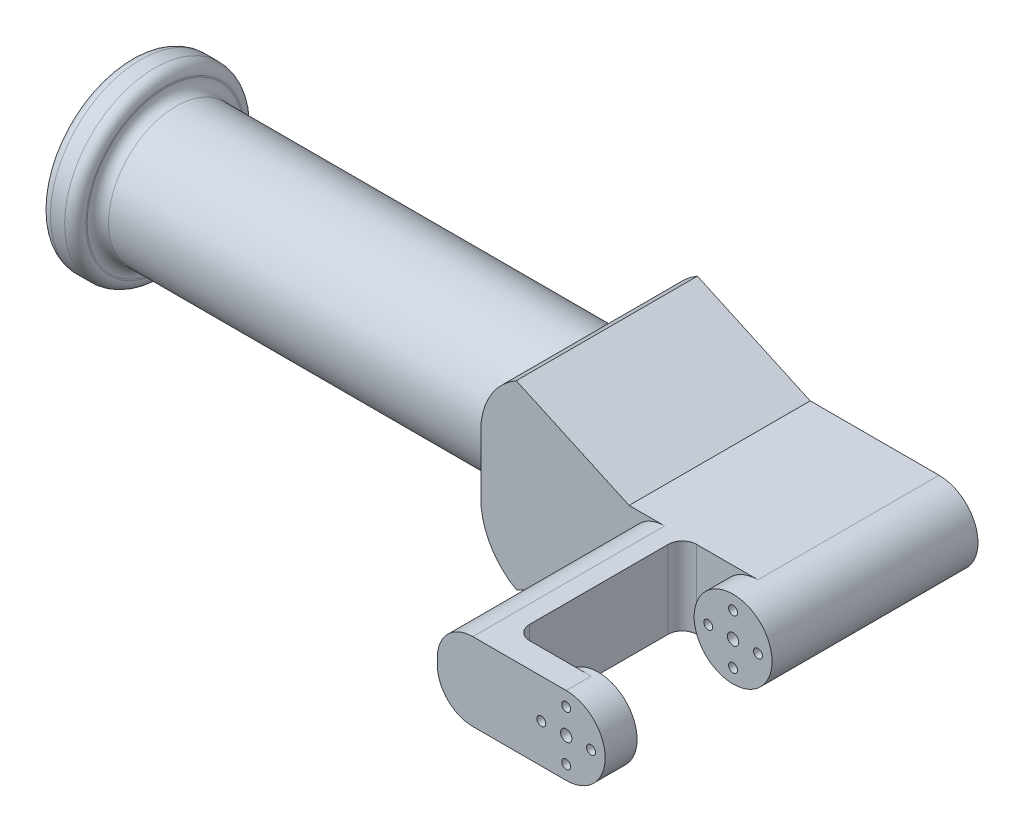
SolidWorks part; units mm, degrees
ref_plane "Front Plane" through (0, 0, 0) normal (0, 0, 1) x (1, 0, 0)
ref_plane "Top Plane" through (0, 0, 0) normal (0, 1, 0) x (1, 0, 0)
ref_plane "Right Plane" through (0, 0, 0) normal (1, 0, 0) x (0, 0, -1)
sketch "Sketch1" plane through (0, 0, 0) normal (1, 0, 0) x (0, 0, -1)
  line L0 (0, 10.97) -> (80, 10.97)
  line L1 (80, 10.97) -> (80, -10.97)
  line L2 (0, -10.97) -> (80, -10.97)
  arc A0 (0, 10.97) -> (0, -10.97) centre (0, 0) ccw
  dimension "D1" = 21.94
  dimension "D2" = 80
extrude "Boss-Extrude1" add sketch "Sketch1" along normal blind 15
sketch "Sketch2" plane through (15, 0, 0) normal (1, 0, 0) x (0, 0, -1)
  line L0 (0, 28.05) -> (0, -28.05) construction
  circle A0 centre (0, 0) radius 10.97
  circle A1 centre (0, 0) radius 1.6
  circle A2 centre (0, 6.58) radius 1.25
  circle A3 centre (6.58, 0) radius 1.25
  circle A4 centre (0, -6.58) radius 1.25
  circle A5 centre (-6.58, 0) radius 1.25
  point P17 (0, 0)
  dimension "D1" = 3.2
  dimension "D2" = 2.5
  dimension "D3" = 6.58
  dimension "D4" = 4
extrude "Boss-Extrude2" add sketch "Sketch2" along normal blind 5.89
sketch "Sketch3" plane through (20.89, 0, 0) normal (1, 0, 0) x (0, 0, -1)
  circle A0 centre (0, 6.58) radius 1.25
  circle A1 centre (0, 0) radius 1.6
  circle A2 centre (0, -6.58) radius 1.25
  circle A3 centre (-6.58, 0) radius 1.25
  circle A4 centre (6.58, 0) radius 1.25
extrude "Cut-Extrude1" cut sketch "Sketch3" against normal blind 100
sketch "Sketch4" plane through (15, 0, 0) normal (1, 0, 0) x (0, 0, -1)
  line L0 (80, 10.97) -> (0, 10.97) construction
  line L1 (30, 10.97) -> (80, 10.97)
  line L2 (30, 10.97) -> (30, -10.97)
  line L3 (30, -10.97) -> (80, -10.97)
  line L4 (80, 10.97) -> (80, -10.97)
  dimension "D1" = 30
extrude "Boss-Extrude3" add sketch "Sketch4" along normal blind 49.02
sketch "Sketch5" plane through (0, 0, 0) normal (0, 1, 0) x (1, 0, 0)
  line L0 (0, -12.067) -> (0, 12.067) construction
  line L1 (64.02, 34.7595) -> (0, 34.7595) construction
  line L2 (64.02, 80) -> (64.02, 30) construction
  line L3 (32.01, 80) -> (32.01, -10.8477) construction
  line L4 (64.02, 80) -> (0, 80) construction
sketch "Sketch6" plane through (0, 10.97, 0) normal (0, 1, 0) x (1, 0, 0)
  line L0 (64.02, 80) -> (0, 80) construction
  line L1 (15, 30) -> (44, 30)
  line L2 (15, 30) -> (15, 80)
  line L3 (15, 80) -> (44, 80)
  line L4 (44, 30) -> (44, 80)
sketch "Sketch9" plane through (0, 0, 0) normal (-1, 0, 0) x (0, 0, 1)
  line L0 (-80, 0) -> (10.8477, 0) construction
  line L1 (-80, 25.5) -> (-29, 25.5)
  line L2 (-80, 25.5) -> (-80, -25.5)
  line L3 (-80, -25.5) -> (-29, -25.5)
  line L4 (-29, 25.5) -> (-29, -25.5)
  line L5 (-80, 25.5) -> (-29, -25.5) construction
  line L6 (-80, -25.5) -> (-29, 25.5) construction
  line L7 (-80, 10.97) -> (-80, -10.97) construction
  point P0 (-54.5, 0)
  dimension "D1" = 29
  dimension "D2" = 25.5
  dimension "D3" = 0
extrude "Boss-Extrude7" add sketch "Sketch9" along normal blind 10
sketch "Sketch10" plane through (-10, 0, 0) normal (-1, 0, 0) x (0, 0, 1)
  line L0 (-80, 0) -> (-29, 0) construction
  line L1 (-80, 10.97) -> (-80, -10.97) construction
  line L2 (-29, -25.5) -> (-29, 25.5) construction
  circle A0 centre (-54.5, 0) radius 19.05
  dimension "D1" = 38.1
extrude "Boss-Extrude8" add sketch "Sketch10" along normal blind 114.3
sketch "Sketch11" plane through (-124.3, 0, 0) normal (-1, 0, 0) x (0, 0, 1)
  line L0 (-73.55, 0) -> (-35.45, 0) construction
  line L1 (-80, 0) -> (10.8477, 0) construction
  circle A0 centre (-54.5, 0) radius 19.05 construction
  circle A1 centre (-54.5, 0) radius 25.4
  dimension "D1" = 50.8
extrude "Boss-Extrude9" add sketch "Sketch11" along normal blind 10
sketch "Sketch12" plane through (0, 0, -30) normal (0, 0, 1) x (1, 0, 0)
  line L0 (64.02, -10.97) -> (15, -10.97) construction
  line L1 (64.02, 10.97) -> (49.02, 10.97)
  line L2 (64.02, 10.97) -> (64.02, -10.97)
  line L3 (64.02, -10.97) -> (49.02, -10.97)
  line L4 (49.02, 10.97) -> (49.02, -10.97)
  dimension "D1" = 15
extrude "Boss-Extrude10" add sketch "Sketch12" along normal blind 30
sketch "Sketch13" plane through (64.02, 0, 0) normal (1, 0, 0) x (0, 0, -1)
  circle A0 centre (0, 0) radius 10.97
  circle A1 centre (0, 0) radius 1.6
  circle A2 centre (6.58, 0) radius 1.25
  circle A3 centre (0, 6.58) radius 1.25
  circle A4 centre (0, -6.58) radius 1.25
  circle A5 centre (-6.58, 0) radius 1.25
  point P17 (0, 0)
  dimension "D1" = 4
extrude "Boss-Extrude11" add sketch "Sketch13" against normal blind 20.89
sketch "Sketch15" plane through (64.02, 0, 0) normal (1, 0, 0) x (0, 0, -1)
  circle A0 centre (0, 0) radius 1.6
  circle A1 centre (0, 6.58) radius 1.25
  circle A2 centre (6.58, 0) radius 1.25
  circle A3 centre (0, -6.58) radius 1.25
  circle A4 centre (-6.58, 0) radius 1.25
  point P15 (0, 0)
  dimension "D1" = 4
extrude "Cut-Extrude2" cut sketch "Sketch15" against normal blind 20.89
sketch "Sketch17" plane through (0, 0, 0) normal (1, 0, 0) x (0, 0, -1)
  line L1 (29, 25.5) -> (80, 25.5)
  line L2 (29, 25.5) -> (29, -25.5)
  line L3 (29, -25.5) -> (80, -25.5)
  line L4 (80, 25.5) -> (80, -25.5)
extrude "Boss-Extrude12" add sketch "Sketch17" along normal blind 79.02
sketch "Sketch18" plane through (0, 0, -29) normal (0, 0, 1) x (1, 0, 0)
  line L1 (39.5513, 13.4042) -> (70.044, 13.4042)
  line L2 (39.5513, 13.4042) -> (39.5513, -17.0884)
  line L3 (39.5513, -17.0884) -> (70.044, -17.0884)
  line L4 (70.044, 13.4042) -> (70.044, -17.0884)
extrude "Cut-Extrude3" cut sketch "Sketch18" along normal blind 64
sketch "Sketch19" plane through (0, 0, -29) normal (0, 0, 1) x (1, 0, 0)
  line L0 (79.02, 25.5) -> (79.02, -25.5) construction
  line L1 (79.02, 10.97) -> (64.02, 10.97)
  line L2 (79.02, 10.97) -> (79.02, -10.97)
  line L3 (79.02, -10.97) -> (64.02, -10.97)
  line L4 (64.02, 10.97) -> (64.02, -10.97)
  line L5 (50.0335, 0) -> (-50.0335, 0) construction
  dimension "D1" = 15
  dimension "D2" = 21.94
  dimension "D3" = 10.97
extrude "Boss-Extrude13" add sketch "Sketch19" along normal blind 29
sketch "Sketch20" plane through (79.02, 0, 0) normal (1, 0, 0) x (0, 0, -1)
  circle A0 centre (0, 0) radius 10.97
  circle A1 centre (0, 0) radius 1.6
  circle A2 centre (0, 6.58) radius 1.25
  circle A3 centre (6.58, 0) radius 1.25
  circle A4 centre (0, -6.58) radius 1.25
  circle A5 centre (-6.58, 0) radius 1.25
  point P17 (0, 0)
  dimension "D1" = 4
extrude "Boss-Extrude14" add sketch "Sketch20" against normal blind 20.98
sketch "Sketch21" plane through (79.02, 0, 0) normal (1, 0, 0) x (0, 0, -1)
  circle A0 centre (0, 0) radius 1.6
  circle A1 centre (0, 6.58) radius 1.25
  circle A2 centre (6.58, 0) radius 1.25
  circle A3 centre (0, -6.58) radius 1.25
  circle A4 centre (-6.58, 0) radius 1.25
  point P14 (0, 0)
  dimension "D1" = 4
extrude "Cut-Extrude4" cut sketch "Sketch21" against normal blind 20.98
sketch "Sketch23" plane through (79.02, 0, 0) normal (1, 0, 0) x (0, 0, -1)
  line L0 (29, -10.97) -> (29, -25.5) construction
  line L1 (-13.4821, 15.5896) -> (29, 15.5896)
  line L2 (-13.4821, 15.5896) -> (-13.4821, -18.235)
  line L3 (-13.4821, -18.235) -> (29, -18.235)
  line L4 (29, 15.5896) -> (29, -18.235)
extrude "Cut-Extrude6" cut sketch "Sketch23" against normal blind 100
sketch "Sketch27" plane through (0, 0, -29) normal (0, 0, 1) x (1, 0, 0)
  line L1 (44, 0) -> (-44, 0) construction
  line L2 (25.67, 18.75) -> (52.37, 18.75)
  line L3 (25.67, 18.75) -> (25.67, -18.75)
  line L4 (25.67, -18.75) -> (52.37, -18.75)
  line L5 (52.37, 18.75) -> (52.37, -18.75)
  line L6 (25.67, 18.75) -> (52.37, -18.75) construction
  line L7 (25.67, -18.75) -> (52.37, 18.75) construction
  line L8 (79.02, 25.5) -> (79.02, -25.5) construction
  point P2 (39.02, 0)
  dimension "D1" = 26.7
  dimension "D2" = 37.5
  dimension "D3" = 40
sketch "Sketch24" plane through (0, 25.5, 0) normal (0, 1, 0) x (1, 0, 0)
  line L0 (-10, 54.5) -> (79.02, 54.5) construction
  line L1 (-10, 29) -> (-10, 80) construction
  line L2 (79.02, 80) -> (79.02, 29) construction
  circle A0 centre (34.51, 54.5) radius 1.6
  circle A1 centre (34.51, 61.08) radius 1.25
  circle A2 centre (41.09, 54.5) radius 1.25
  circle A3 centre (34.51, 47.92) radius 1.25
  circle A4 centre (27.93, 54.5) radius 1.25
  dimension "D1" = 3.2
  dimension "D2" = 2.5
  dimension "D3" = 6.58
  dimension "D4" = 4
sketch "Sketch31" plane through (0, 25.5, 0) normal (0, 1, 0) x (1, 0, 0)
  line L0 (-28.05, 0) -> (28.05, 0) construction
  line L1 (-10, 80) -> (40.8, 80)
  line L2 (-10, 80) -> (-10, 0)
  line L3 (-10, 0) -> (40.8, 0)
  line L4 (40.8, 80) -> (40.8, 0)
  dimension "D1" = 50.8
sketch "Sketch32" plane through (0, 25.5, 0) normal (0, 1, 0) x (1, 0, 0)
  line L0 (-10, 80) -> (79.02, 80) construction
  line L1 (79.02, 29) -> (40.8, 29)
  line L2 (79.02, 29) -> (79.02, 80)
  line L3 (79.02, 80) -> (40.8, 80)
  line L4 (40.8, 29) -> (40.8, 80)
sketch "Sketch38" plane through (-10, 0, 0) normal (-1, 0, 0) x (0, 0, 1)
  line L0 (-80, -25.5) -> (-10.8, -25.5) construction
  line L5 (-80, 25.5) -> (-53.9876, 25.5)
  line L6 (-80, 25.5) -> (-80, -25.5)
  line L7 (-80, -25.5) -> (-53.9876, -25.5)
  line L8 (-53.9876, 25.5) -> (-53.9876, -25.5)
  circle A2 centre (-53.9876, 0) radius 25.5
fillet "Fillet6" radius 3 2 edges at (-124.3, 0, -29.1) (-124.3, 0, -35.45)
fillet "Fillet7" radius 3 1 edges at (-134.3, 0, -29.1)
sketch "Sketch40" plane through (0, 25.5, 0) normal (0, 1, 0) x (1, 0, 0)
  line L0 (0, -28.05) -> (0, 28.05) construction
  line L1 (79.02, 80) -> (0, 80)
  line L2 (79.02, 80) -> (79.02, 39)
  line L3 (79.02, 39) -> (0, 39)
  line L4 (0, 80) -> (0, 39)
  line L6 (79.02, 29) -> (40.8, 29) construction
  dimension "D1" = 10
sketch "Sketch41" plane through (0, 0, -29) normal (0, 0, 1) x (1, 0, 0)
  line L0 (28.05, 0) -> (-28.05, 0) construction
  line L1 (79.02, 25.5) -> (79.02, -25.5) construction
  line L2 (0, -28.05) -> (0, 28.05) construction
  line L3 (-10, 25.5) -> (79.02, 25.5)
  line L4 (-10, 25.5) -> (-10, -25.5)
  line L5 (-10, -25.5) -> (79.02, -25.5)
  line L6 (79.02, 25.5) -> (79.02, -25.5)
  line L7 (0, 25.5) -> (79.02, 25.5)
  line L8 (0, 25.5) -> (0, -25.5)
  line L9 (0, -25.5) -> (79.02, -25.5)
  line L10 (79.02, 25.5) -> (79.02, -25.5)
  line L11 (0, -25.5) -> (31.7741, -10.97)
  line L12 (0, 25.5) -> (31.7741, 10.97)
  line L13 (68.05, 10.97) -> (31.7741, 10.97)
  line L15 (31.7741, -10.97) -> (68.05, -10.97)
  circle A0 centre (68.05, 0) radius 10.97
  dimension "D1" = 21.94
  dimension "D2" = 10.97
extrude "Cut-Extrude16" cut sketch "Sketch41" against normal blind 100
fillet "Fillet9" radius 20 1 edges at (-10, 25.5, -54.5)
fillet "Fillet10" radius 20 1 edges at (-10, -25.5, -54.5)
sketch "Sketch45" plane through (0, 0, -29) normal (0, 0, 1) x (1, 0, 0)
  line L0 (31.7741, 10.97) -> (31.7741, -10.97)
  line L1 (31.7741, -10.97) -> (46.7741, -10.97)
  line L2 (31.7741, -10.97) -> (68.05, -10.97) construction
  line L3 (46.7741, -10.97) -> (46.7741, 10.97)
  line L4 (68.05, 10.97) -> (31.7741, 10.97) construction
  line L5 (46.7741, 10.97) -> (31.7741, 10.97)
  dimension "D1" = 15
extrude "Boss-Extrude19" add sketch "Sketch45" along normal blind 54
sketch "Sketch46" plane through (46.7741, 0, 0) normal (1, 0, 0) x (0, 0, -1)
  line L0 (-25, -10.97) -> (29, -10.97) construction
  line L1 (-25, 10.97) -> (-18, 10.97)
  line L2 (-25, 10.97) -> (-25, -10.97)
  line L3 (-25, -10.97) -> (-18, -10.97)
  line L4 (-18, 10.97) -> (-18, -10.97)
  dimension "D1" = 7
extrude "Boss-Extrude20" add sketch "Sketch46" along normal up to vertex (21.2759 mm away) up to point (68.05, 10.97, -29)
sketch "Sketch47" plane through (0, 0, 18) normal (0, 0, -1) x (-1, 0, 0)
  line L0 (-68.05, -10.97) -> (-68.05, 10.97) construction
  circle A0 centre (-68.05, 0) radius 10.97
  dimension "D1" = 21.94
extrude "Boss-Extrude21" add sketch "Sketch47" along normal blind 2 and the other way up to surface (7 mm away) other way up to face at (49.9121, 0, 25)
fillet "Fillet11" radius 10 2 edges at (31.7741, -10.97, -2) (31.7741, 10.97, -2)
fillet "Fillet12" radius 4 2 edges at (46.7741, 0, 18) (46.7741, 0, -29)
sketch "Sketch50" plane through (0, 0, -29) normal (0, 0, 1) x (1, 0, 0)
  circle A0 centre (68.05, 0) radius 10.97
extrude "Boss-Extrude22" add sketch "Sketch50" along normal blind 7
sketch "Sketch51" plane through (0, 0, -22) normal (0, 0, 1) x (1, 0, 0)
  line L0 (68.05, 0) -> (68.05, 7) construction
  circle A0 centre (68.05, 0) radius 1.6
  circle A1 centre (68.05, 7) radius 1.25
  circle A2 centre (75.05, 0) radius 1.25
  circle A3 centre (68.05, -7) radius 1.25
  circle A4 centre (61.05, 0) radius 1.25
  dimension "D1" = 3.2
  dimension "D3" = 2.5
  dimension "D4" = 4
  dimension "D2" = 7
extrude "Cut-Extrude18" cut sketch "Sketch51" against normal through all both and the other way through all
